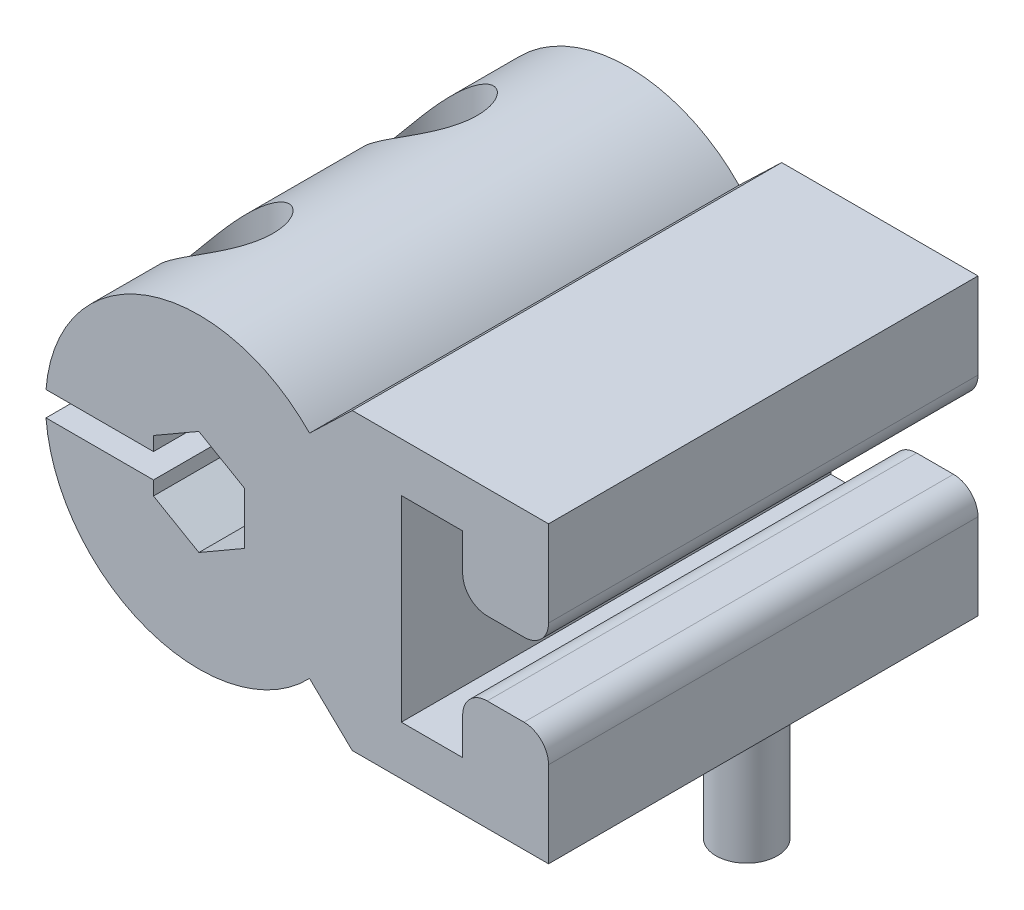
SolidWorks part; units mm, degrees
ref_plane "Front Plane" through (0, 0, 0) normal (0, 0, 1) x (1, 0, 0)
ref_plane "Top Plane" through (0, 0, 0) normal (0, 1, 0) x (1, 0, 0)
ref_plane "Right Plane" through (0, 0, 0) normal (1, 0, 0) x (0, 0, -1)
sketch "Sketch1" plane through (0, 0, 0) normal (0, 0, 1) x (1, 0, 0)
  line L0 (-20.2969, 1) -> (-3.7, 1)
  line L1 (-3.7, 2.1362) -> (-3.7, 1)
  line L2 (-3.7, -2.1362) -> (0, -4.2724)
  line L3 (0, -4.2724) -> (3.7, -2.1362)
  line L4 (3.7, -2.1362) -> (3.7, 2.1362)
  line L5 (3.7, 2.1362) -> (0, 4.2724)
  line L6 (0, 4.2724) -> (-3.7, 2.1362)
  line L7 (-3.7, 0) -> (-22.8855, 0) construction
  line L8 (-20.2969, -1) -> (-3.7, -1)
  line L9 (-20.2969, 1) -> (-20.2969, -1)
  line L10 (-3.7, -1) -> (-3.7, -2.1362)
  arc A0 (-1.85, -3.2043) -> (-1.85, 3.2043) centre (0, 0) ccw construction
  circle A1 centre (0, 0) radius 12.5
  dimension "D2" = 25
  dimension "D1" = 7.4
  dimension "D3" = 1
extrude "Boss-Extrude1" add sketch "Sketch1" along normal blind 35 contours L8 A1 L0 L1 L6 L5 L4 L3 L2 L10 region at (0.4863, 12.137, 0)
ref_plane "Plane1" through (0, 12.5, 0) normal (0, 1, 0) x (1, 0, 0)
sketch "Sketch2" plane through (0, 12.5, 0) normal (0, 1, 0) x (1, 0, 0)
  line L0 (-12.4599, 0) -> (-7.0788, -9.1755) construction
  line L1 (-7.0788, -9.1755) -> (-7.0788, -25.8245) construction
  line L2 (-7.0788, -25.8245) -> (-12.4599, -35) construction
  circle A0 centre (-7.0788, -9.1755) radius 1.8669
  circle A1 centre (-7.0788, -25.8245) radius 1.8669
  dimension "D1" = 3.7338
extrude "Cut-Extrude1" cut sketch "Sketch2" against normal through all
sketch "Sketch3" plane through (0, 12.5, 0) normal (0, 1, 0) x (1, 0, 0)
  circle A0 centre (-7.0788, -9.1755) radius 3.9497
  circle A1 centre (-7.0788, -25.8245) radius 3.9497
  dimension "D1" = 7.8994
extrude "Cut-Extrude2" cut sketch "Sketch3" against normal blind 8
ref_plane "Plane2" through (0, -12.5, 0) normal (0, -1, 0) x (-1, 0, 0)
sketch "Sketch4" plane through (0, -12.5, 0) normal (0, -1, 0) x (-1, 0, 0)
  line L1 (7.0788, -5.2307) -> (3.6625, -7.2031)
  line L2 (3.6625, -7.2031) -> (3.6625, -11.1479)
  line L3 (3.6625, -11.1479) -> (7.0788, -13.1203)
  line L4 (7.0788, -13.1203) -> (10.4951, -11.1479)
  line L5 (10.4951, -11.1479) -> (10.4951, -7.2031)
  line L6 (10.4951, -7.2031) -> (7.0788, -5.2307)
  line L7 (7.0788, -21.8797) -> (3.6625, -23.8521)
  line L8 (3.6625, -23.8521) -> (3.6625, -27.7969)
  line L9 (3.6625, -27.7969) -> (7.0788, -29.7693)
  line L10 (7.0788, -29.7693) -> (10.4951, -27.7969)
  line L11 (10.4951, -27.7969) -> (10.4951, -23.8521)
  line L12 (10.4951, -23.8521) -> (7.0788, -21.8797)
  circle A0 centre (7.0788, -9.1755) radius 3.4163 construction
  circle A1 centre (7.0788, -25.8245) radius 3.4163 construction
  dimension "D1" = 6.8326
extrude "Cut-Extrude3" cut sketch "Sketch4" against normal blind 8
sketch "Sketch5" plane through (0, 0, 0) normal (0, 0, -1) x (-1, 0, 0)
  line L0 (-12.5, -12) -> (-9.0173, -8.6566) construction
  line L5 (-9.0173, 8.6566) -> (-12.5, 12) construction
  line L6 (-21.5, 3) -> (-21.5, 8)
  line L19 (-12.5, -12) -> (-28.5, -12)
  line L21 (-12.5, 12) -> (-28.5, 12)
  line L22 (-28.5, -12) -> (-28.5, -3)
  line L23 (-16.5, -8) -> (-21.5, -8)
  line L24 (-16.5, -8) -> (-16.5, 8)
  line L25 (-16.5, 8) -> (-21.5, 8)
  line L26 (-21.5, -8) -> (-21.5, -3)
  line L27 (-21.5, -3) -> (-28.5, -3)
  line L29 (-21.5, 3) -> (-28.5, 3)
  line L31 (-28.5, 3) -> (-28.5, 12)
  line L32 (-12.5, -12) -> (-9.0173, -8.6566)
  line L33 (-9.0173, 8.6566) -> (-12.5, 12)
  arc A0 (12.4599, 1) -> (12.4599, -1) centre (0, 0) ccw construction
  arc A1 (-9.0173, 8.6566) -> (-9.0173, -8.6566) centre (0, 0) ccw
  dimension "D5" = 7
  dimension "D1" = 16
  dimension "D2" = 24
  dimension "D3" = 6
  dimension "D6" = 12
extrude "Boss-Extrude2" add sketch "Sketch5" against normal through all
fillet "Fillet1" radius 2 4 edges at (21.5, -3, 17.5) (21.5, 3, 17.5) (28.5, 3, 17.5) (28.5, -3, 17.5)
sketch "Sketch6" plane through (0, -12, 0) normal (0, -1, 0) x (1, 0, 0)
  circle A0 centre (21.7627, 12.1144) radius 2.5
  dimension "D1" = 5
extrude "Boss-Extrude3" add sketch "Sketch6" along normal blind 13
fillet "Fillet2" radius 2 1 edges at (21.7627, -12, 9.6144)
